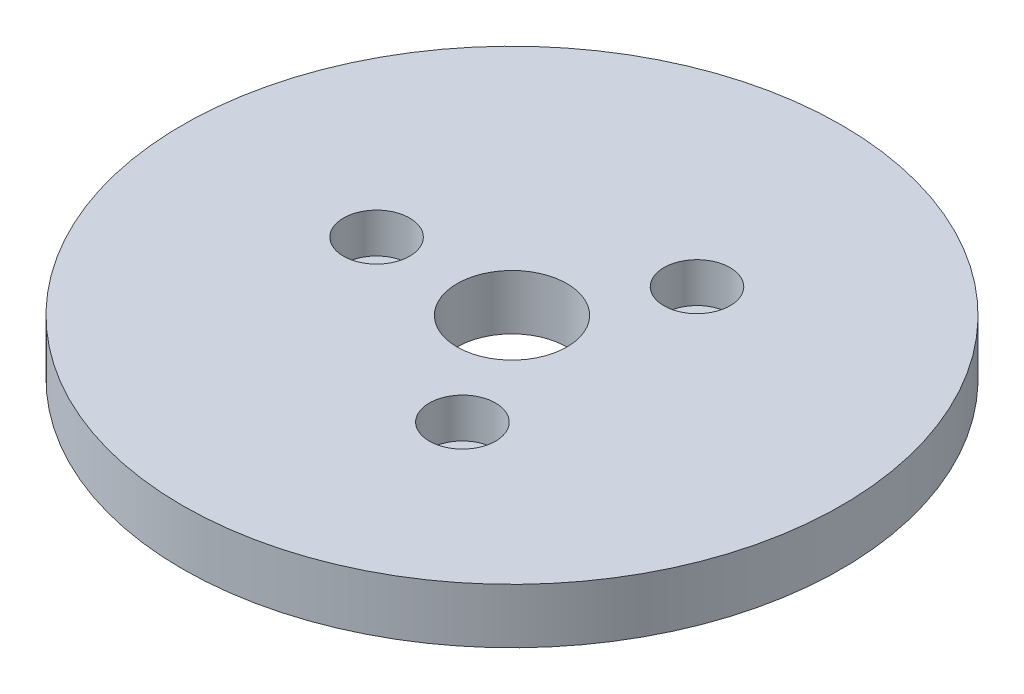
SolidWorks part; units mm, degrees
ref_plane "Front Plane" through (0, 0, 0) normal (0, 0, 1) x (1, 0, 0)
ref_plane "Top Plane" through (0, 0, 0) normal (0, 1, 0) x (1, 0, 0)
ref_plane "Right Plane" through (0, 0, 0) normal (1, 0, 0) x (0, 0, -1)
sketch "Sketch1" plane through (0, 0, 0) normal (0, 1, 0) x (1, 0, 0)
  circle A0 centre (0, 0) radius 60
  dimension "FLANGE_OD" = 120
extrude "Boss-Extrude1" add sketch "Sketch1" along normal blind 10
sketch "Sketch2" plane through (0, 0, 0) normal (0, 1, 0) x (1, 0, 0)
  circle A0 centre (0, 0) radius 10
  dimension "BORE_D" = 20
extrude "Cut-Extrude1" cut sketch "Sketch2" along normal through all
sketch "Sketch3" plane through (0, 10, 0) normal (0, 1, 0) x (1, 0, 0)
  circle A0 centre (0, 0) radius 24.6552 construction
  circle A1 centre (-24.6552, 0) radius 6.027
  dimension "BOLT_D" = 12.054
  dimension "BOLT_PCD" = 49.3103
extrude "Cut-Extrude2" cut sketch "Sketch3" against normal blind 7.2395
pattern_circular "CirPattern1" count 3 over 360 about axis through (0, 0, 0) along (0, 1, 0) of "Cut-Extrude2"
